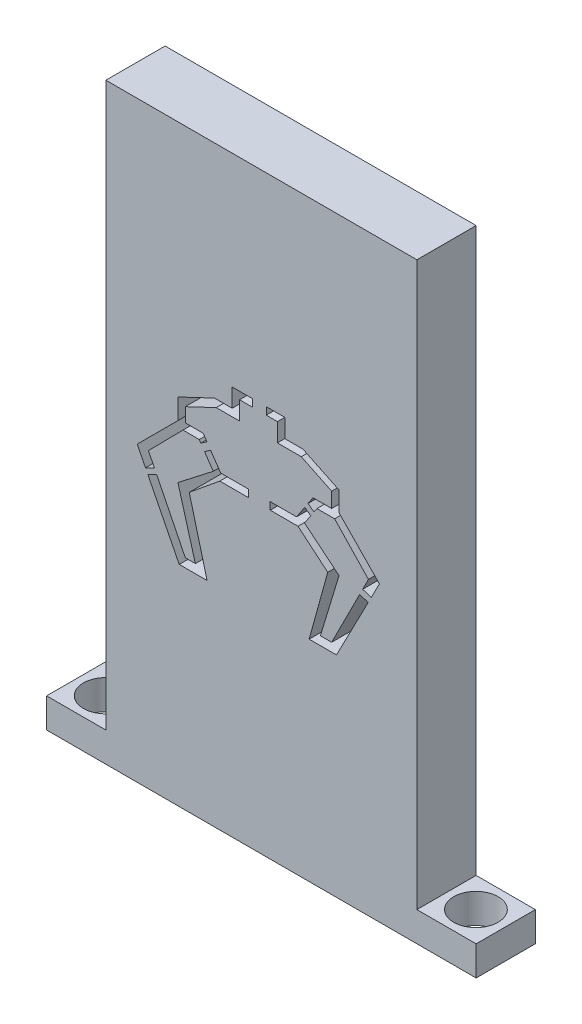
SolidWorks part; units mm, degrees
ref_plane "Plan de face" through (0, 0, 0) normal (0, 0, 1) x (1, 0, 0)
ref_plane "Plan de dessus" through (0, 0, 0) normal (0, 1, 0) x (1, 0, 0)
ref_plane "Plan de droite" through (0, 0, 0) normal (1, 0, 0) x (0, 0, -1)
sketch "Sketch1" plane through (0, 0, 0) normal (0, 1, 0) x (1, 0, 0)
  line L1 (0, 0) -> (29, 0)
  line L2 (0, 0) -> (0, 4)
  line L3 (0, 4) -> (29, 4)
  line L4 (29, 0) -> (29, 4)
  line L5 (4, 0) -> (25, 0)
  line L6 (4, 0) -> (4, 4)
  line L7 (4, 4) -> (25, 4)
  line L8 (25, 0) -> (25, 4)
  circle A0 centre (1.9855, 2) radius 1.5
  circle A1 centre (26.9855, 2) radius 1.5
  point P13 (0, 0)
  point P14 (0, 2)
  point P15 (0, 0)
  point P16 (3.188, 2)
  point P17 (1.9855, 2)
  dimension "D5" = 3
  dimension "D6" = 3
  dimension "D1" = 4
  dimension "D2" = 4
  dimension "D3" = 29
  dimension "D4" = 4
  dimension "D7" = 25
extrude "Boss-Extrude1" add sketch "Sketch1" along normal blind 2 contours L1 L8 L3 L6 | L1 L6 L3 L2 A0 | L8 L1 L4 L3 A1 region at (0.0566, 0, -2) region at (14.5, 0, -2) region at (25.0566, 0, -2)
extrude "Boss-Extrude2" add sketch "Sketch1<3>" along normal blind 40 contours L1 L8 L3 L6 region at (14.5, 0, -2)
sketch "Sketch1<3>" plane through (0, 0, 0) normal (0, 1, 0) x (1, 0, 0) same geometry as "Sketch1"
sketch "Sketch4" plane through (0, 0, 0) normal (0, 0, 1) x (1, 0, 0)
  line L0 (7.9376, 41.4694) -> (22.176, 41.4694) construction
  line L1 (15.5803, 25.8266) -> (13.0273, 25.8266)
  line L2 (13.0273, 25.8266) -> (13.0273, 24.5806)
  line L3 (13.0273, 24.5806) -> (11.4514, 24.5806)
  line L4 (11.4514, 24.5806) -> (9.3626, 23.5911)
  line L5 (9.3626, 23.5911) -> (9.3626, 22.6459)
  line L6 (9.3626, 22.6459) -> (10.5695, 22.6372)
  line L7 (10.5695, 22.6372) -> (11.7528, 20.9037)
  line L8 (11.7528, 20.9037) -> (16.8752, 20.9037)
  line L9 (16.8752, 20.9037) -> (17.9828, 22.5772)
  line L10 (17.9828, 22.5772) -> (19.245, 22.5772)
  line L11 (19.245, 22.5772) -> (19.245, 23.5911)
  line L12 (19.245, 23.5911) -> (17.1928, 24.5806)
  line L13 (17.1928, 24.5806) -> (15.5803, 24.5806)
  line L14 (15.5803, 24.5806) -> (15.5803, 25.8266)
  line L15 (16.0803, 25.0806) -> (16.0803, 26.3266)
  line L16 (16.0803, 26.3266) -> (12.5273, 26.3266)
  line L17 (12.5273, 26.3266) -> (12.5273, 25.0806)
  line L18 (12.5273, 25.0806) -> (11.339, 25.0806)
  line L19 (11.339, 25.0806) -> (8.8626, 23.9075)
  line L20 (8.8626, 23.9075) -> (8.8626, 22.1495)
  line L21 (8.8626, 22.1495) -> (10.3041, 22.1391)
  line L22 (10.3041, 22.1391) -> (11.4887, 20.4037)
  line L23 (11.4887, 20.4037) -> (17.1438, 20.4037)
  line L24 (17.1438, 20.4037) -> (18.2515, 22.0772)
  line L25 (18.2515, 22.0772) -> (19.745, 22.0772)
  line L26 (19.745, 22.0772) -> (19.745, 23.9051)
  line L27 (19.745, 23.9051) -> (17.307, 25.0806)
  line L28 (17.307, 25.0806) -> (16.0803, 25.0806)
  line L29 (8.8626, 22.5246) -> (6.1156, 19.7777)
  line L30 (6.1156, 19.7777) -> (8.9528, 14.1608)
  line L31 (8.9528, 14.1608) -> (10.8334, 14.1608)
  line L32 (10.8334, 14.1608) -> (9.6292, 18.7139)
  line L33 (9.6292, 18.7139) -> (11.6913, 20.4037)
  line L34 (9.2088, 22.147) -> (6.8742, 19.7777)
  line L35 (6.8742, 19.7777) -> (9.3626, 14.7546)
  line L36 (9.3626, 14.7546) -> (10.0416, 14.7546)
  line L37 (10.0416, 14.7546) -> (8.8626, 18.9036)
  line L38 (8.8626, 18.9036) -> (11.2497, 20.7538)
  line L39 (16.9717, 20.4037) -> (18.9808, 18.7139)
  line L40 (18.9808, 18.7139) -> (17.7247, 14.1773)
  line L41 (17.7247, 14.1773) -> (19.5696, 14.1773)
  line L42 (19.5696, 14.1773) -> (22.471, 19.7777)
  line L43 (22.471, 19.7777) -> (19.745, 22.5772)
  line L44 (17.4151, 20.8136) -> (19.745, 18.9036)
  line L45 (19.745, 18.9036) -> (18.4822, 14.7546)
  line L46 (18.4822, 14.7546) -> (19.245, 14.7546)
  line L47 (19.245, 14.7546) -> (21.7289, 19.6735)
  line L48 (21.7289, 19.6735) -> (19.4446, 22.0772)
  line L49 (15.0976, 20.9037) -> (15.0976, 20.4037)
  line L50 (15.0976, 20.4037) -> (13.6343, 20.4037)
  line L51 (13.6343, 20.4037) -> (13.6343, 20.9037)
  line L52 (13.6343, 20.9037) -> (15.0976, 20.9037)
  line L53 (14.8298, 25.8266) -> (14.8298, 26.3266)
  line L54 (14.8298, 26.3266) -> (13.9172, 26.3266)
  line L55 (13.9172, 26.3266) -> (13.9172, 25.8266)
  line L56 (13.9172, 25.8266) -> (14.8298, 25.8266)
  line L57 (10.4112, 21.9822) -> (10.8242, 22.2641)
  line L58 (10.8242, 22.2641) -> (11.0759, 21.8953)
  line L59 (11.0759, 21.8953) -> (10.6629, 21.6134)
  line L60 (10.6629, 21.6134) -> (10.4112, 21.9822)
  line L61 (18.0518, 21.7756) -> (17.8348, 21.4476)
  line L62 (17.8348, 21.4476) -> (17.429, 21.7405)
  line L63 (17.429, 21.7405) -> (17.6501, 22.0746)
  line L64 (17.6501, 22.0746) -> (18.0518, 21.7756)
  line L65 (7.2734, 18.9718) -> (6.6753, 18.6697)
  line L66 (6.6753, 18.6697) -> (6.8305, 18.3624)
  line L67 (6.8305, 18.3624) -> (7.4286, 18.6587)
  line L68 (7.4286, 18.6587) -> (7.2734, 18.9718)
  line L69 (21.3401, 18.9036) -> (21.9199, 18.7139)
  line L70 (21.9199, 18.7139) -> (21.712, 18.3127)
  line L71 (21.712, 18.3127) -> (21.1368, 18.5009)
  line L72 (21.1368, 18.5009) -> (21.3401, 18.9036)
  dimension "D1" = 0.5
extrude "Cut-Extrude1" cut sketch "Sketch4" against normal through all both and the other way through all contours L48 L47 L46 L45 L44 L24 L23 L39 L40 L41 L42 L43 L26 L25 | L38 L37 L36 L35 L34 L21 L20 L29 L30 L31 L32 L33 L23 L22 | L7 L59 L22 L23 L51 L8 | L22 L57 L7 L6 L5 L4 L3 L2 L1 L55 L16 L17 L18 L19 L20 L21 | L9 L64 L24 L25 L26 L27 L28 L15 L16 L53 L1 L14 L13 L12 L11 L10 | L24 L62 L9 L8 L49 L23 | L65 L35 L34 L21 L20 L29 L30 | L47 L69 L42 L43 L26 L25 L48 region at (15.2051, 25.8936, 0) region at (13.4722, 25.8932, 0) region at (21.1427, 20.569, 0) region at (16.5269, 20.8217, 0) region at (7.4244, 20.5212, 0) region at (18.5284, 19.7955, 0) region at (12.0739, 20.867, 0) region at (7.1659, 18.4371, 0)
